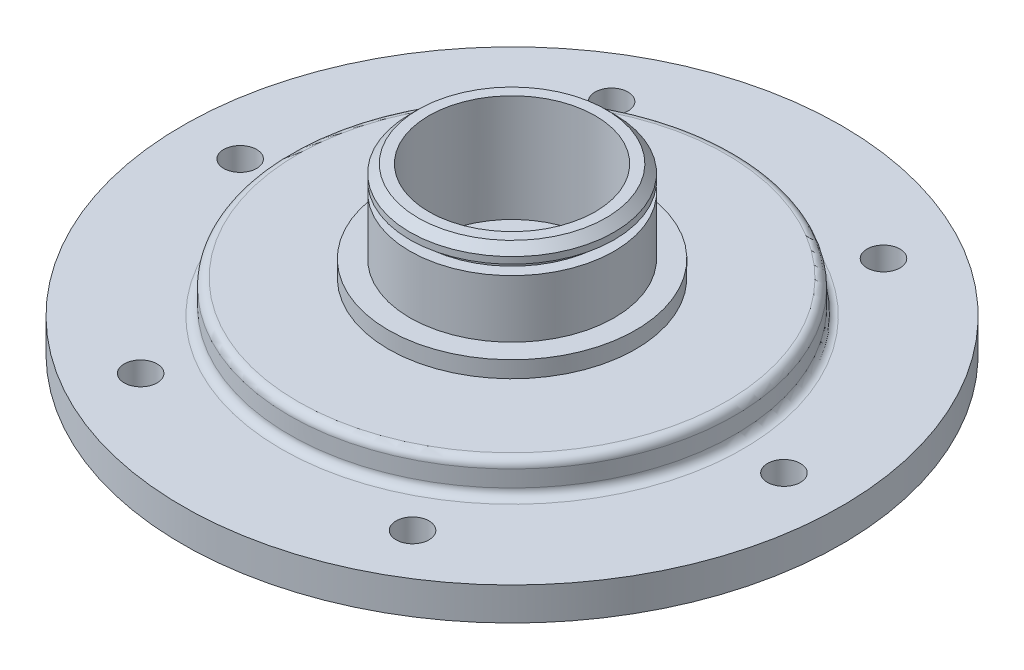
SolidWorks part; units mm, degrees
ref_plane "前视基准面" through (0, 0, 0) normal (0, 0, 1) x (1, 0, 0)
ref_plane "上视基准面" through (0, 0, 0) normal (0, 1, 0) x (1, 0, 0)
ref_plane "右视基准面" through (0, 0, 0) normal (1, 0, 0) x (0, 0, -1)
sketch "草图1" plane through (0, 0, 0) normal (0, 1, 0) x (1, 0, 0)
  circle A0 centre (0, 0) radius 10.1
  circle A1 centre (0, 0) radius 12.4
  dimension "D1" = 24.8
  dimension "D2" = 20.2
extrude "凸台-拉伸1" add sketch "草图1" along normal blind 10
sketch "草图2" plane through (0, 0, 0) normal (0, -1, 0) x (1, 0, 0)
  circle A0 centre (0, 0) radius 10.1 construction
  circle A1 centre (0, 0) radius 10.1
  circle A2 centre (0, 0) radius 15
  dimension "D1" = 30
extrude "凸台-拉伸2" add sketch "草图2" along normal blind 6
sketch "草图3" plane through (0, -6, 0) normal (0, -1, 0) x (1, 0, 0)
  line L0 (0, 0) -> (0, -10.1) construction
  circle A0 centre (0, 0) radius 10.1 construction
  circle A1 centre (0, 0) radius 10.1
  circle A2 centre (0, 0) radius 40
  circle A3 centre (33, 0) radius 2
  circle A4 centre (16.5, -28.5788) radius 2
  circle A5 centre (-16.5, -28.5788) radius 2
  circle A6 centre (-33, 0) radius 2
  circle A7 centre (-16.5, 28.5788) radius 2
  circle A8 centre (16.5, 28.5788) radius 2
  circle A9 centre (33, 0) radius 3.5 construction
  dimension "D1" = 80
  dimension "D2" = 4
  dimension "D5" = 7
  dimension "D4" = 33
  dimension "D3" = 6
extrude "凸台-拉伸3" add sketch "草图3" along normal blind 4
ref_plane "基准面1" through (0, 7, 0) normal (0, 1, 0) x (1, 0, 0)
sketch "草图4" plane through (0, 7, 0) normal (0, 1, 0) x (1, 0, 0)
  circle A2 centre (0, 0) radius 11
  circle A3 centre (0, 0) radius 12.4 construction
  circle A4 centre (0, 0) radius 12.4
  dimension "D1" = 22
extrude "切除-拉伸1" cut sketch "草图4" along normal blind 1.2
chamfer "倒角1" distance 1 angle 45 1 edges at (0, 10, 12.4)
sketch "草图8" plane through (0, -6, 0) normal (0, 1, 0) x (1, 0, 0)
  circle A0 centre (0, 0) radius 27
  circle A1 centre (0, 0) radius 10.1 construction
  circle A2 centre (0, 0) radius 10.1
  dimension "D1" = 54
extrude "凸台-拉伸6" add sketch "草图8" along normal blind 4
sketch "草图9" plane through (0, -10, 0) normal (0, -1, 0) x (1, 0, 0)
  circle A0 centre (0, 0) radius 25
  dimension "D1" = 50
extrude "切除-拉伸3" cut sketch "草图9" against normal blind 5
fillet "圆角1" radius 2.5 2 edges at (0, -10, -25) (0, -5, -25)
fillet "圆角2" radius 1 2 edges at (0, -2, 27) (0, -6, -27)
sketch "草图10" plane through (0, -5, 0) normal (0, -1, 0) x (1, 0, 0)
  circle A0 centre (0, 0) radius 8
  circle A1 centre (0, 0) radius 10.1 construction
  circle A2 centre (0, 0) radius 10.1
  dimension "D1" = 16
extrude "凸台-拉伸7" add sketch "草图10" against normal blind 2
